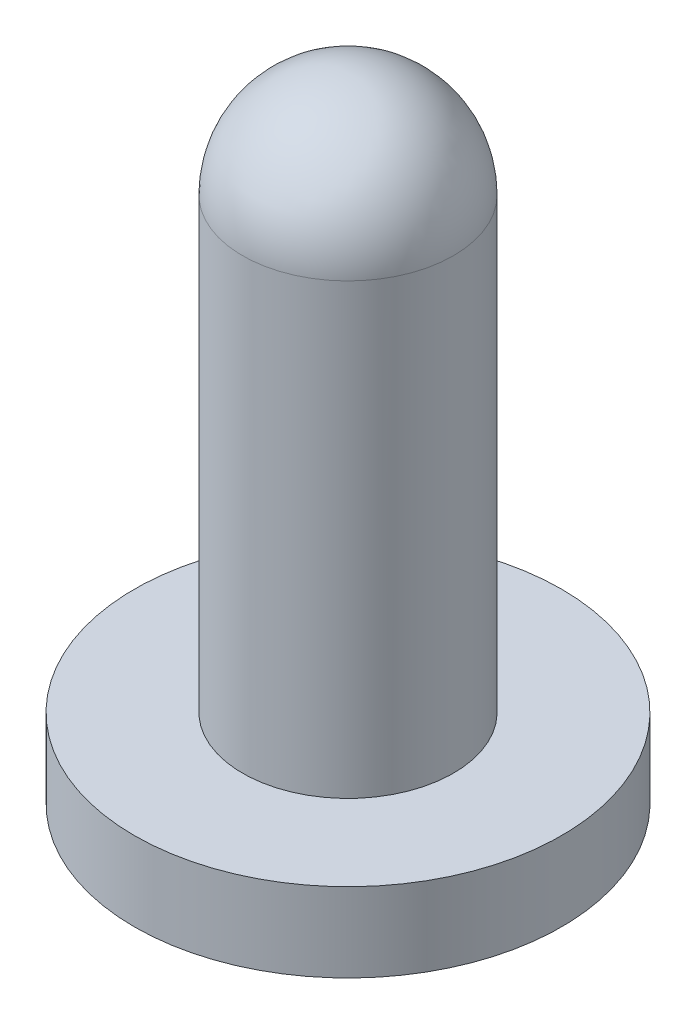
SolidWorks part; units mm, degrees
ref_plane "Front Plane" through (0, 0, 0) normal (0, 0, 1) x (1, 0, 0)
ref_plane "Top Plane" through (0, 0, 0) normal (0, 1, 0) x (1, 0, 0)
ref_plane "Right Plane" through (0, 0, 0) normal (1, 0, 0) x (0, 0, -1)
sketch "Sketch1" plane through (0, 0, 0) normal (0, 1, 0) x (1, 0, 0)
  circle A0 centre (0, 0) radius 2
  dimension "D1" = 4
extrude "Boss-Extrude1" add sketch "Sketch1" along normal blind 12
sketch "Sketch6" plane through (0, 0, 0) normal (0, -1, 0) x (1, 0, 0)
  circle A0 centre (0, 0) radius 4.05
  dimension "D1" = 8.1
extrude "Boss-Extrude3" add sketch "Sketch6" against normal blind 1.5
sketch "Sketch2" plane through (0, 0, 0) normal (0, -1, 0) x (1, 0, 0)
  circle A0 centre (0, 0) radius 1
  dimension "D1" = 2
extrude "Cut-Extrude1" cut sketch "Sketch2" against normal blind 10
draft "Draft1" type of draft neutral plane draft angle 1 faces to draft 1 face at (0, 10, -1) neutral plane through (0, 10, 0) neutral plane normal (0, -1, 0) parameters "D1"=1
sketch "Sketch7" plane through (0, 0, 0) normal (0, 0, 1) x (1, 0, 0)
  line L0 (2, 1.5) -> (2, 12) construction
  line L1 (2, 12) -> (-2, 12) construction
  line L4 (0, 10) -> (0, 12) construction
  line L5 (2, 10) -> (3.0807, 10)
  line L6 (3.0807, 10) -> (3.0807, 13.0807)
  line L7 (3.0807, 13.0807) -> (0, 13.0807)
  line L8 (0, 13.0807) -> (0, 12)
  arc A0 (2, 10) -> (0, 12) centre (0, 10) ccw
  point P5 (3.8101, 10.5)
  point P11 (4.5807, 14.2583)
  dimension "D1" = 3.0807
revolve "Cut-Revolve3" cut sketch "Sketch7" angle 360 about L4
sketch "Sketch3" plane through (0, 10, 0) normal (0, -1, 0) x (1, 0, 0)
  line L0 (1.151, 0.2338) -> (0.746, 0)
  line L1 (0.746, 0) -> (1.151, -0.2338)
  line L2 (0, 0) -> (1.1746, 0) construction
  line L3 (1.151, 0.2338) -> (1.151, -0.2338) construction
  line L6 (-0.373, -1.1138) -> (-0.373, -0.6461)
  line L7 (-0.373, -0.6461) -> (-0.778, -0.8799)
  line L10 (-0.373, -1.1138) -> (-0.778, -0.8799) construction
  line L11 (-0.778, 0.8799) -> (-0.373, 0.6461)
  line L14 (-0.373, 0.6461) -> (-0.373, 1.1138)
  line L15 (-0.778, 0.8799) -> (-0.373, 1.1138) construction
  arc A1 (-0.778, -0.8799) -> (-0.373, -1.1138) centre (0, 0) ccw
  arc A2 (-0.373, 1.1138) -> (-0.778, 0.8799) centre (0, 0) ccw
  circle A7 centre (0, 0) radius 1.1746 construction
  arc A8 (1.151, -0.2338) -> (1.151, 0.2338) centre (0, 0) ccw
  circle A9 centre (0, 0) radius 1 construction
  point P16 (0, 0)
  dimension "D1" = 0.254
extrude "Boss-Extrude2" add sketch "Sketch3" along normal up to surface (10 mm away) up to face at (0, 0, 1.1746)
sketch "ref_for_revolve" plane through (0, 0, 0) normal (0, -1, 0) x (1, 0, 0)
  circle A0 centre (0, 0) radius 1.1746 construction
sketch "Sketch4" plane through (0, 0, 0) normal (0, 0, 1) x (1, 0, 0)
  line L1 (1.1746, 0) -> (0.746, 0.4286)
  line L2 (0.746, 0.4286) -> (0, 0.4286)
  line L4 (0, 0.4286) -> (0, 0)
  line L5 (0.746, 0.4286) -> (0.746, 0) construction
  line L6 (0.746, 0) -> (1.1746, 0) construction
  line L7 (1.1746, 0) -> (0, 0)
  line L8 (-0.373, 0) -> (1.151, 0) construction
  line L9 (-1.1746, 0) -> (1.1746, 0) construction
  point P7 (0, 0)
  point P8 (1.2819, 0)
  point P12 (0, 0)
  point P13 (1.368, 0)
  point P14 (1.1559, 0)
  point P17 (0, 0)
revolve "Cut-Revolve1" cut sketch "Sketch4" angle 360 about L4
